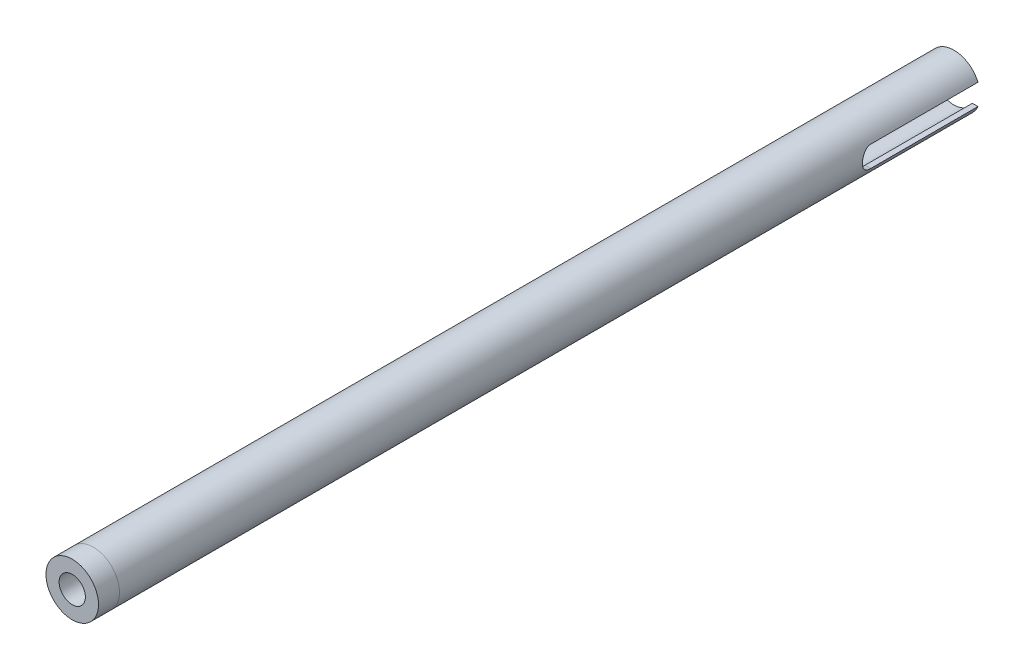
SolidWorks part; units mm, degrees
material "AISI 4130 Steel, annealed at 865C"
ref_plane "Front Plane" through (0, 0, 0) normal (0, 0, 1) x (1, 0, 0)
ref_plane "Top Plane" through (0, 0, 0) normal (0, 1, 0) x (1, 0, 0)
ref_plane "Right Plane" through (0, 0, 0) normal (1, 0, 0) x (0, 0, -1)
sketch "Axis" plane through (0, 0, 0) normal (0, 1, 0) x (1, 0, 0)
  line L0 (0, 0) -> (0, 266.3368) construction
  line L1 (0, 0) -> (0, -34.925) construction
  line L2 (0, 266.3368) -> (-7.9375, 266.3368) construction
  line L4 (0, 288.6784) -> (-10.3188, 259.6343) construction
  dimension "D1" = 34.925
  dimension "D2" = 7.9375
sketch "Sketch1" plane through (0, 0, 0) normal (0, 0, 1) x (1, 0, 0)
  line L0 (-7.9375, 0) -> (7.9375, 0) construction
  line L1 (-7.2748, 3.175) -> (7.2748, 3.175)
  line L2 (-7.2748, -3.175) -> (7.2748, -3.175)
  circle A0 centre (0, 0) radius 7.9375
  circle A1 centre (0, 0) radius 6.4135
  circle A2 centre (0, 0) radius 3.9688
  dimension "D1" = 15.875
  dimension "D3" = 7.9375
  dimension "D2" = 1.524
  dimension "D4" = 6.35
extrude "Threaded insert 1-1" add sketch "Sketch1" against normal blind 6.35 contours A2 L1 A1 | A1 L1 A0 | A2 L0 A1 L1 | A1 L0 A0 L1 | L0 A1 L2 A0 | L0 A2 L2 A1 | A2 L2 A1 | A1 L2 A0 | L0 A1 L2 A2 | L0 A0 L2 A1 | A0 L0 A1 L1 | A1 L0 A2 L1 region at (4.7887, 1.6543, 0) region at (4.7887, -1.6543, 0) region at (6.9234, 1.6163, 0) region at (6.9234, -1.6163, 0) region at (-4.7887, -1.6543, 0) region at (-4.7887, 1.6543, 0) region at (0, 4.6159, 0) region at (0, -4.6159, 0) region at (0, 6.5666, 0) region at (6.4237, -3.3281, 0) region at (-6.9234, -1.6163, 0) region at (-6.9234, 1.6163, 0)
extrude "Threaded insert 1-2" add sketch "Sketch1<3>" against normal blind 9.525 from surface contours A2 L1 A1 | A2 L0 A1 L1 | L0 A2 L2 A1 | A2 L2 A1 | L0 A1 L2 A2 | A1 L0 A2 L1 region at (4.7887, 1.6543, 0) region at (4.7887, -1.6543, 0) region at (-4.7887, -1.6543, 0) region at (-4.7887, 1.6543, 0) region at (0, 4.6159, 0) region at (0, -4.6159, 0) starting at face at (7.9375, 0, -6.35)
sketch "Sketch1<3>" plane through (0, 0, 0) normal (0, 0, 1) x (1, 0, 0) same geometry as "Sketch1"
extrude "A-arm tube" add sketch "Sketch1<4>" against normal up to vertex (266.3368 mm away) from surface separate body contours A1 L1 A0 | A1 L0 A0 L1 | L0 A1 L2 A0 | A1 L2 A0 | L0 A0 L2 A1 | A0 L0 A1 L1 region at (6.9234, 1.6163, 0) region at (6.9234, -1.6163, 0) region at (0, 6.5666, 0) region at (6.4237, -3.3281, 0) region at (-6.9234, -1.6163, 0) region at (-6.9234, 1.6163, 0) up to point (0, 0, -266.3368) starting at face at (6.4135, 0, -6.35)
sketch "Sketch1<4>" plane through (0, 0, 0) normal (0, 0, 1) x (1, 0, 0) same geometry as "Sketch1"
extrude "Apex slot" cut sketch "Sketch1<5>" along normal blind 35.56 from surface contours A0 L0 A1 L1 | L0 A0 L2 A1 | A1 L0 A0 L1 | L0 A1 L2 A0 region at (6.9234, 1.6163, 0) region at (6.9234, -1.6163, 0) region at (-6.9234, -1.6163, 0) region at (-6.9234, 1.6163, 0) starting at face at (6.4135, 0, -266.3368)
sketch "Sketch1<5>" plane through (0, 0, 0) normal (0, 0, 1) x (1, 0, 0) same geometry as "Sketch1"
fillet "Fillet1" radius 3.175 4 edges at (-6.4237, 3.175, -230.7768) (-6.4237, -3.175, -230.7768) (6.4237, -3.175, -230.7768) (6.4237, 3.175, -230.7768)
equation "\"tube diameter\"= 5 / 8"
equation "\"tube thickness\"= .06"
equation "\"apex thickness\"= .25"
equation "\"tube slot\"= 1.4"
equation "\"D1@Sketch1\"=\"tube diameter\""
equation "\"D2@Sketch1\"=\"tube thickness\""
equation "\"threaded insert hole\"= .3125"
equation "\"D3@Sketch1\"=\"threaded insert hole\""
equation "\"D4@Sketch1\"=\"apex thickness\""
equation "\"D1@Apex slot\" = \"tube slot\""
equation "\"D1@Fillet1\"=\"apex thickness\"/2"
